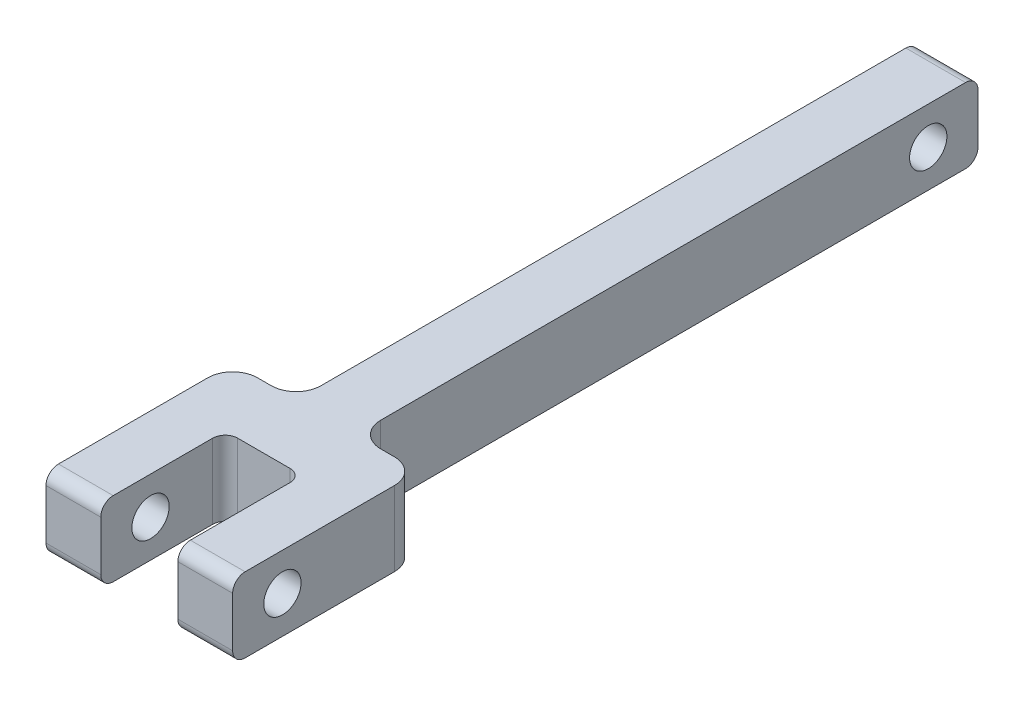
SolidWorks part; units mm, degrees
ref_plane "Alzado" through (0, 0, 0) normal (0, 0, 1) x (1, 0, 0)
ref_plane "Planta" through (0, 0, 0) normal (0, 1, 0) x (1, 0, 0)
ref_plane "Vista lateral" through (0, 0, 0) normal (1, 0, 0) x (0, 0, -1)
sketch "Croquis1" plane through (0, 0, 0) normal (1, 0, 0) x (0, 0, -1)
  line L0 (-31.5, 3) -> (31.5, 3)
  line L2 (-32.5, 0) -> (32.5, 0) construction
  line L3 (-32.5, 2) -> (-32.5, -2)
  line L4 (-31.5, -3) -> (31.5, -3)
  line L5 (32.5, 2) -> (32.5, -2)
  arc A0 (-32.5, -2) -> (-31.5, -3) centre (-31.5, -2) ccw
  arc A1 (-32.5, 2) -> (-31.5, 3) centre (-31.5, 2) cw
  arc A2 (31.5, -3) -> (32.5, -2) centre (31.5, -2) ccw
  arc A3 (31.5, 3) -> (32.5, 2) centre (31.5, 2) cw
  point P1 (0, 0)
  point P9 (-32.5, -3)
  point P13 (-32.5, 3)
  point P16 (32.5, -3)
  point P19 (32.5, 3)
  dimension "D3" = 1
  dimension "D4" = 1
  dimension "D1" = 3
  dimension "D2" = 65
extrude "Saliente-Extruir1" add sketch "Croquis1" along normal mid plane 4.8
sketch "Croquis2" plane through (0, 0, 0) normal (1, 0, 0) x (0, 0, -1)
  line L0 (-32.5, 2) -> (-32.5, -2) construction
  line L1 (32.5, -2) -> (32.5, 2) construction
  circle A0 centre (-28.5, 0) radius 1.5
  circle A1 centre (28.5, 0) radius 1.5
  dimension "D1" = 3
  dimension "D3" = 3
  dimension "D2" = 4
  dimension "D4" = 4
extrude "Cortar-Extruir1" cut sketch "Croquis2" against normal through all both and the other way through all
sketch "Croquis3" plane through (0, 0, 0) normal (1, 0, 0) x (0, 0, -1)
  line L0 (-32.5, 2) -> (-32.5, -2) construction
  line L1 (-32.5, 2) -> (-32.5, -2)
  line L2 (-31.5, 3) -> (-17.5, 3)
  line L3 (31.5, 3) -> (-31.5, 3) construction
  line L4 (-17.5, 3) -> (-17.5, -3)
  line L5 (-31.5, -3) -> (31.5, -3) construction
  line L6 (-17.5, -3) -> (-31.5, -3)
  circle A0 centre (-28.5, 0) radius 1.5 construction
  circle A1 centre (-28.5, 0) radius 1.5
  arc A2 (-31.5, 3) -> (-32.5, 2) centre (-31.5, 2) ccw construction
  arc A3 (-31.5, 3) -> (-32.5, 2) centre (-31.5, 2) ccw
  arc A4 (-32.5, -2) -> (-31.5, -3) centre (-31.5, -2) ccw construction
  arc A5 (-32.5, -2) -> (-31.5, -3) centre (-31.5, -2) ccw
  dimension "D1" = 15
extrude "Saliente-Extruir2" add sketch "Croquis3" along normal mid plane 15
sketch "Croquis4" plane through (0, 0, 0) normal (1, 0, 0) x (0, 0, -1)
  line L0 (-31.5, 3) -> (-22.5, 3)
  line L1 (-17.5, 3) -> (-31.5, 3) construction
  line L2 (-22.5, 3) -> (-22.5, -3)
  line L3 (-31.5, -3) -> (-17.5, -3) construction
  line L4 (-32.5, 2) -> (-32.5, -2)
  line L5 (-31.5, -3) -> (-17.5, -3)
  line L6 (-17.5, -3) -> (-17.5, 3)
  line L7 (-17.5, 3) -> (-31.5, 3)
  line L8 (-32.5, 2) -> (-32.5, -2)
  line L12 (-22.5, -3) -> (-31.5, -3)
  arc A2 (-31.5, 3) -> (-32.5, 2) centre (-31.5, 2) ccw
  arc A3 (-32.5, -2) -> (-31.5, -3) centre (-31.5, -2) ccw
  arc A4 (-31.5, 3) -> (-32.5, 2) centre (-31.5, 2) ccw
  arc A5 (-32.5, -2) -> (-31.5, -3) centre (-31.5, -2) ccw
  dimension "D2" = 10
  dimension "D1" = 0
extrude "Cortar-Extruir2" cut sketch "Croquis4" against normal mid plane 6.2
fillet "Redondeo1" radius 2 4 edges at (2.4, 0, 17.5) (-2.4, 0, 17.5) (7.5, 0, 17.5) (-7.5, 0, 17.5)
fillet "Redondeo2" radius 1 2 edges at (3.1, 0, 22.5) (-3.1, 0, 22.5)
